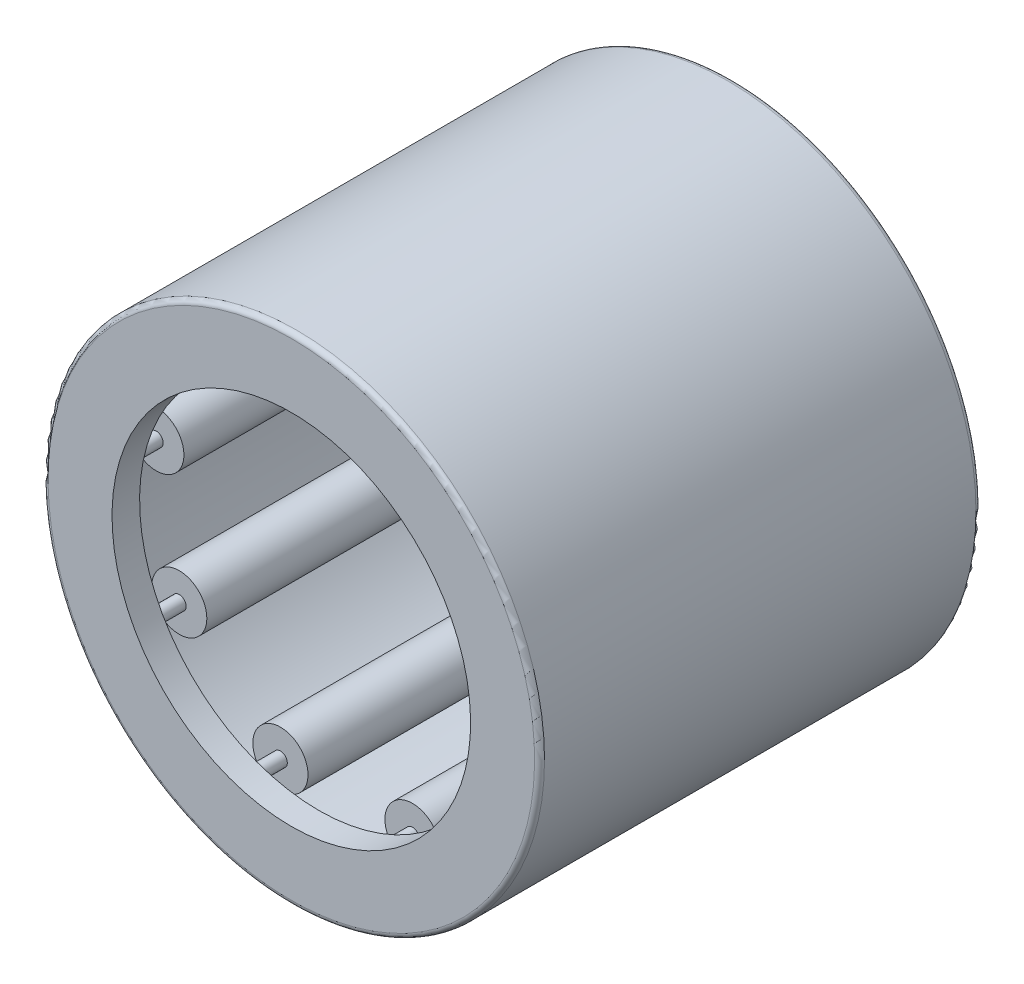
SolidWorks part; units mm, degrees
ref_plane "Front Plane" through (0, 0, 0) normal (0, 0, 1) x (1, 0, 0)
ref_plane "Top Plane" through (0, 0, 0) normal (0, 1, 0) x (1, 0, 0)
ref_plane "Right Plane" through (0, 0, 0) normal (1, 0, 0) x (0, 0, -1)
sketch "Sketch1" plane through (0, 0, 0) normal (1, 0, 0) x (0, 0, -1)
  line L0 (-6.35, 0) -> (6.35, 0) construction
  line L1 (0, 0) -> (0, 7.1438) construction
  line L2 (-6.35, 0) -> (-6.35, 7.1438) construction
  line L3 (-6.35, 7.1438) -> (6.35, 7.1438)
  line L4 (6.35, 7.1438) -> (6.35, 0) construction
  line L5 (6.35, 0) -> (5.5562, 0) construction
  line L6 (5.5562, 0) -> (5.5563, 6.35) construction
  line L7 (5.5563, 6.35) -> (-5.5563, 6.35)
  line L8 (-5.5563, 6.35) -> (-5.5562, 0) construction
  line L9 (-5.5562, 0) -> (-6.35, 0) construction
  line L10 (-6.35, 7.1438) -> (-6.35, 5.1594)
  line L11 (-6.35, 5.1594) -> (-5.5563, 5.1594)
  line L12 (-5.5563, 5.1594) -> (-5.5563, 6.35)
  line L13 (5.5562, 7.1438) -> (5.5563, 6.35) construction
  line L14 (5.5563, 6.35) -> (5.5563, 5.1594)
  line L15 (5.5563, 5.1594) -> (6.35, 5.1594)
  line L16 (6.35, 5.1594) -> (6.35, 7.1438)
  line L17 (5.5563, 6.35) -> (5.5563, 5.5563) construction
  line L18 (5.5563, 5.5563) -> (5.5562, 4.7625) construction
  line L19 (5.5563, -6.35) -> (5.5563, -5.5563) construction
  line L20 (5.5562, -7.1438) -> (5.5563, -6.35) construction
  line L21 (6.35, -5.1594) -> (6.35, -7.1438) construction
  line L22 (5.5563, -5.1594) -> (6.35, -5.1594) construction
  line L23 (5.5563, -6.35) -> (5.5563, -5.1594) construction
  line L24 (-5.5563, -5.1594) -> (-5.5563, -6.35) construction
  line L25 (-6.35, -5.1594) -> (-5.5563, -5.1594) construction
  line L26 (-6.35, -7.1438) -> (-6.35, -5.1594) construction
  line L27 (5.5563, -6.35) -> (-5.5563, -6.35) construction
  line L28 (-6.35, -7.1438) -> (6.35, -7.1438) construction
  point P5 (0, 4.7625)
  dimension "Width" = 12.7
  dimension "OD" = 14.2875
  dimension "Shaft Dia" = 9.525
revolve "Revolve1" add sketch "Sketch1" angle 360 about L0
sketch "Sketch2" plane through (0, 0, 0) normal (1, 0, 0) x (0, 0, -1)
  line L0 (5.5563, 6.35) -> (-5.5563, 6.35) construction
  line L1 (-4.7625, 5.5563) -> (4.7625, 5.5563) construction
  line L2 (-4.7625, 5.5563) -> (-4.7625, 6.35) construction
  line L3 (-4.7625, 6.35) -> (4.7625, 6.35)
  line L4 (4.7625, 5.5563) -> (4.7625, 6.35) construction
  line L5 (5.5563, 5.1594) -> (6.35, 5.1594) construction
  line L6 (-5.5563, 5.5563) -> (-4.7625, 5.5563) construction
  line L7 (4.7625, 5.5563) -> (5.5563, 5.5563) construction
  line L8 (-6.35, 5.1594) -> (-5.5563, 5.1594) construction
  line L9 (-4.7625, 5.7547) -> (-4.7625, 5.3578) construction
  line L10 (-5.5563, 5.5563) -> (-5.5563, 5.1594) construction
  line L11 (-4.7625, 6.35) -> (-4.7625, 5.7547)
  line L12 (4.7625, 6.35) -> (4.7625, 5.7547)
  line L13 (4.7625, 5.7547) -> (-4.7625, 5.7547)
  line L14 (0, 6.35) -> (0, 4.7625) construction
  line L15 (-5.5563, 5.1594) -> (-5.5563, 6.35) construction
  line L16 (-4.7625, 5.3578) -> (-5.5563, 5.3578) construction
  line L17 (0, 0) -> (6.35, 0) construction
  line L18 (-4.7625, -5.3578) -> (-5.5563, -5.3578) construction
  line L19 (0, -6.35) -> (0, -4.7625) construction
  line L20 (-5.5562, -5.5563) -> (-5.5563, -5.1594) construction
  line L21 (-4.7625, -5.7547) -> (-4.7625, -5.3578) construction
  line L22 (4.7625, -5.5563) -> (5.5563, -5.5563) construction
  line L23 (-5.5562, -5.5563) -> (-4.7625, -5.5563) construction
  line L24 (4.7625, -5.5563) -> (4.7625, -6.35) construction
  line L25 (-4.7625, -5.5563) -> (-4.7625, -6.35) construction
  line L26 (-4.7625, -5.5563) -> (4.7625, -5.5563) construction
  line L27 (4.7625, -5.7547) -> (-4.7625, -5.7547) construction
  line L28 (4.7625, -6.35) -> (4.7625, -5.7547) construction
  line L29 (-4.7625, -6.35) -> (-4.7625, -5.7547) construction
  line L30 (-4.7625, -6.35) -> (4.7625, -6.35) construction
  line L31 (6.35, -7.1437) -> (6.35, 7.1438) construction
  point P16 (0, 5.5563)
revolve "Revolve2" add sketch "Sketch2" angle 360 about L1
sketch "Sketch3" plane through (0, 0, 0) normal (1, 0, 0) x (0, 0, -1)
  line L0 (5.5563, 6.35) -> (5.5563, 5.1594) construction
  line L1 (-5.5563, 5.5563) -> (5.5563, 5.5563)
  line L2 (-5.5563, 5.5563) -> (-5.5563, 5.7547)
  line L3 (-5.5563, 5.7547) -> (5.5563, 5.7547)
  line L4 (5.5563, 5.5563) -> (5.5563, 5.7547)
  line L5 (0, 0) -> (6.35, 0) construction
  line L6 (6.35, -7.1437) -> (6.35, 7.1438) construction
  line L7 (5.5563, -5.5563) -> (5.5563, -5.7547) construction
  line L8 (-5.5563, -5.7547) -> (5.5563, -5.7547) construction
  line L9 (-5.5563, -5.5563) -> (-5.5563, -5.7547) construction
  line L10 (-5.5563, -5.5563) -> (5.5563, -5.5563) construction
revolve "Revolve3" add sketch "Sketch3" angle 360 about L1
ref_axis "Axis1" through (0, 0, -6.35) along (0, 0, 1)
pattern_circular "CirPattern1" count 9 every 40 about axis through (0, 0, -6.35) along (0, 0, 1) of bodies 166 167
fillet "Fillet1" radius 0.1429 2 edges at (0, -7.1437, -6.35) (0, -7.1438, 6.35)
sketch "Sketch4" plane through (0, 0, 0) normal (1, 0, 0) x (0, 0, -1)
  line L1 (6.2071, 4.7625) -> (4.7625, 4.7625)
  line L2 (6.2071, 4.7625) -> (6.2071, 5.1594)
  line L3 (6.2071, 5.1594) -> (4.7625, 5.1594)
  line L4 (4.7625, 4.7625) -> (4.7625, 5.1594)
  line L5 (-6.35, 5.1594) -> (-5.5563, 5.1594) construction
  line L6 (6.2071, -7.1438) -> (6.2071, 7.1438) construction
  line L7 (4.7625, 6.35) -> (4.7625, 5.7547) construction
revolve "Revolve4" [suppressed] add sketch "Sketch4" angle 360 about L0
sketch "Sketch5" plane through (0, 0, 0) normal (1, 0, 0) x (0, 0, -1)
  line L0 (-6.2071, 7.1438) -> (-6.2071, -7.1438) construction
  line L1 (-4.7625, 4.7625) -> (-6.2071, 4.7625)
  line L2 (-4.7625, 4.7625) -> (-4.7625, 5.1594)
  line L3 (-4.7625, 5.1594) -> (-6.2071, 5.1594)
  line L4 (-6.2071, 4.7625) -> (-6.2071, 5.1594)
  line L6 (-4.7625, 6.35) -> (-4.7625, 5.7547) construction
  line L7 (-6.35, 5.1594) -> (-5.5563, 5.1594) construction
revolve "Revolve5" [suppressed] add sketch "Sketch5" angle 360 about L0
equation "\"Rollers@CirPattern1\" = \"OD@Sketch1\"*16"
equation "\"D1@Fillet1\" = \"OD@Sketch1\"*.01"
